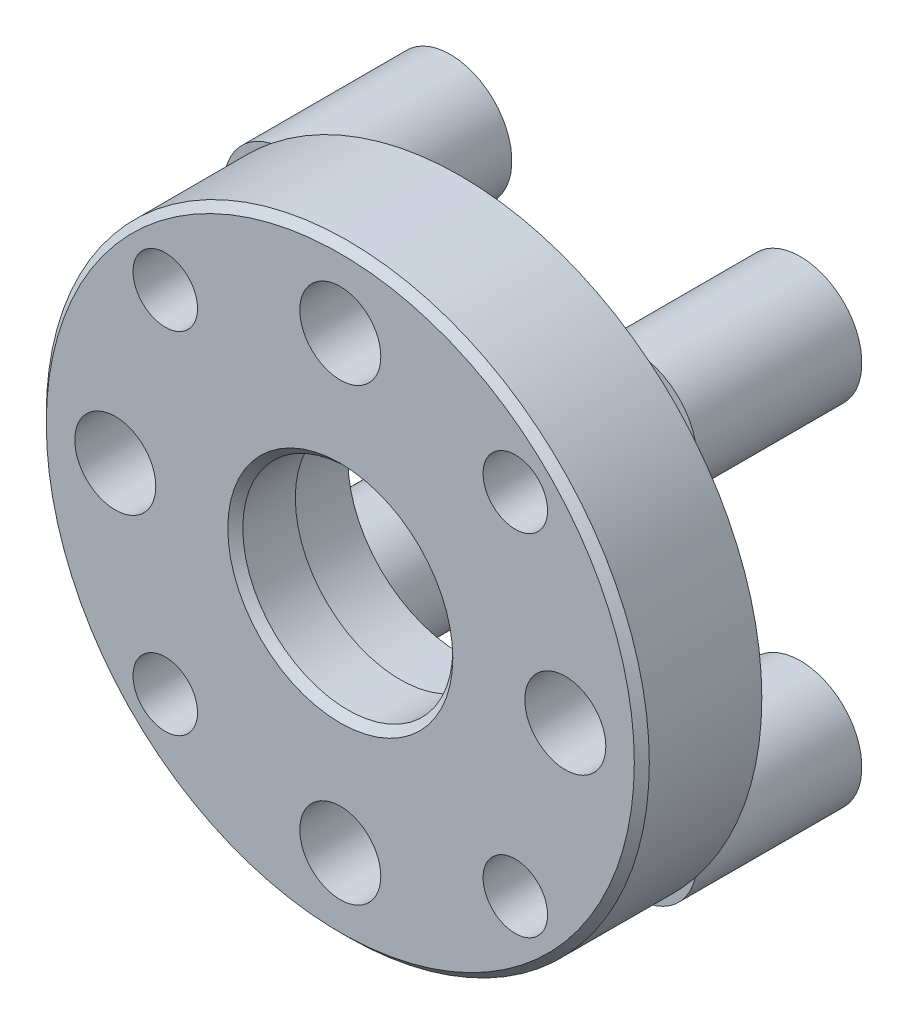
SolidWorks part; units mm, degrees
material "ABS"
ref_plane "Front Plane" through (0, 0, 0) normal (0, 0, 1) x (1, 0, 0)
ref_plane "Top Plane" through (0, 0, 0) normal (0, 1, 0) x (1, 0, 0)
ref_plane "Right Plane" through (0, 0, 0) normal (1, 0, 0) x (0, 0, -1)
ref_plane "Output Plane" through (0, 0, -162.4475) normal (0, 0, -1) x (-1, 0, 0)
sketch "CYC Output Sketch" plane through (0, 0, -162.4475) normal (0, 0, 1) x (1, 0, 0)
  line L1 (11.6673, 11.6673) -> (-11.6673, 11.6673) construction
  line L2 (-11.6673, 11.6673) -> (-11.6673, -11.6673) construction
  line L3 (-11.6673, -11.6673) -> (11.6673, -11.6673) construction
  line L4 (11.6673, -11.6673) -> (11.6673, 11.6673) construction
  circle A0 centre (0, 0) radius 16.5 construction
sketch "Sketch3" plane through (0, 0, -162.4475) normal (0, 0, -1) x (-1, 0, 0)
  circle A0 centre (-11.6673, 11.6673) radius 4
  circle A1 centre (11.6673, 11.6673) radius 4
  circle A2 centre (11.6673, -11.6673) radius 4
  circle A3 centre (-11.6673, -11.6673) radius 4
  dimension "D1" = 8
extrude "Boss-Extrude1" add sketch "Sketch3" along normal blind 11
sketch "Sketch6" plane through (0, 0, -162.4475) normal (0, 0, 1) x (1, 0, 0)
  arc A0 (10.7357, 16.9928) -> (-16.9928, 10.7357) centre (0, 0) ccw
  arc A18 (16.9928, -10.7357) -> (10.7357, 16.9928) centre (0, 0) ccw
  arc A19 (-10.7357, -16.9928) -> (16.9928, -10.7357) centre (0, 0) ccw
  arc A20 (-16.9928, 10.7357) -> (-10.7357, -16.9928) centre (0, 0) ccw
  circle A23 centre (0, 0) radius 7.5
  dimension "D2" = 40.2
  dimension "D1" = 15
extrude "Boss-Extrude6" add sketch "Sketch6" along normal blind 8 contours A23 | A0 A20 A19 A18 region at (0, 0, -162.4475)
sketch "Sketch8" plane through (0, 0, -154.4475) normal (0, 0, 1) x (1, 0, 0)
  line L0 (0, 0) -> (11.6673, 11.6673) construction
  line L1 (0, 0) -> (16.5, 0) construction
  circle A0 centre (0, 0) radius 16.5 construction
  circle A1 centre (11.6673, 11.6673) radius 1.6
  circle A2 centre (11.6673, -11.6673) radius 1.6
  circle A3 centre (-11.6673, -11.6673) radius 1.6
  circle A4 centre (-11.6673, 11.6673) radius 1.6
  point P16 (0, 0)
  dimension "D1" = 33
  dimension "D2" = 45
  dimension "D3" = 3.2
  dimension "D4" = 4
extrude "Cut-Extrude1" cut sketch "Sketch8" against normal through all
sketch "Sketch9" plane through (0, 0, -173.4475) normal (0, 0, 1) x (1, 0, 0)
  circle A0 centre (11.6673, 11.6673) radius 3
  circle A1 centre (11.6673, -11.6673) radius 3
  circle A2 centre (-11.6673, -11.6673) radius 3
  circle A3 centre (-11.6673, 11.6673) radius 3
  point P12 (0, 0)
  dimension "D1" = 6
  dimension "D2" = 4
extrude "Cut-Extrude2" cut sketch "Sketch9" along normal blind 3 from surface starting at face at (13.2673, 11.6673, -173.4475)
sketch "Sketch10" plane through (0, 0, -173.4475) normal (0, 0, -1) x (-1, 0, 0)
  circle A0 centre (11.6673, 11.6673) radius 4.1
  circle A1 centre (11.6673, 11.6673) radius 4
  circle A2 centre (11.6673, -11.6673) radius 4
  circle A3 centre (11.6673, -11.6673) radius 4.1
  circle A4 centre (-11.6673, -11.6673) radius 4
  circle A5 centre (-11.6673, -11.6673) radius 4.1
  circle A6 centre (-11.6673, 11.6673) radius 4
  circle A7 centre (-11.6673, 11.6673) radius 4.1
  point P16 (0, 0)
  dimension "D1" = 8
  dimension "D2" = 8.2
  dimension "D3" = 4
extrude "Boss-Extrude8" add sketch "Sketch10" against normal blind 11
sketch "Sketch11" plane through (0, 0, -154.4475) normal (0, 0, 1) x (1, 0, 0)
  line L0 (0, 0) -> (0, 15) construction
  circle A0 centre (0, 15) radius 2.7
  circle A1 centre (15, 0) radius 2.7
  circle A2 centre (0, -15) radius 2.7
  circle A3 centre (-15, 0) radius 2.7
  circle A4 centre (-11.6673, 11.6673) radius 2.15
  circle A5 centre (11.6673, 11.6673) radius 2.15
  circle A6 centre (11.6673, -11.6673) radius 2.15
  circle A7 centre (-11.6673, -11.6673) radius 2.15
  point P13 (0, 0)
  dimension "D2" = 5.4
  dimension "D4" = 4.3
  dimension "D1" = 15
  dimension "D3" = 4
extrude "Cut-Extrude3" cut sketch "Sketch11" against normal blind 8
sketch "Sketch12" plane through (0, 0, -154.4475) normal (0, 0, 1) x (1, 0, 0)
  circle A0 centre (0, 0) radius 7.5
  circle A1 centre (0, 0) radius 7
  dimension "D1" = 15
  dimension "D2" = 14
extrude "Boss-Extrude9" add sketch "Sketch12" against normal blind 4
chamfer "Chamfer1" distance 0.5 angle 45 2 edges at (7, 0, -154.4475) (20.1, 0, -154.4475)
equation "\"RingPinShaft\"= 5.05"
equation "\"CenterBearingOut\"=32.00"
equation "\"RingPostIn\"=5.15"
equation "\"CamBearingOut\"=15.1"
equation "\"DiskOutputShaft\"=10.1"
equation "\"CenterShaft\"=25.2"
equation "\"Eccentricity\"=2"
equation "\"CycCamShaft\"=10.05"
equation "\"D2@Sketch6\"=\"OutputBearing\""
equation "\"OutputBearing\"=40.2"
